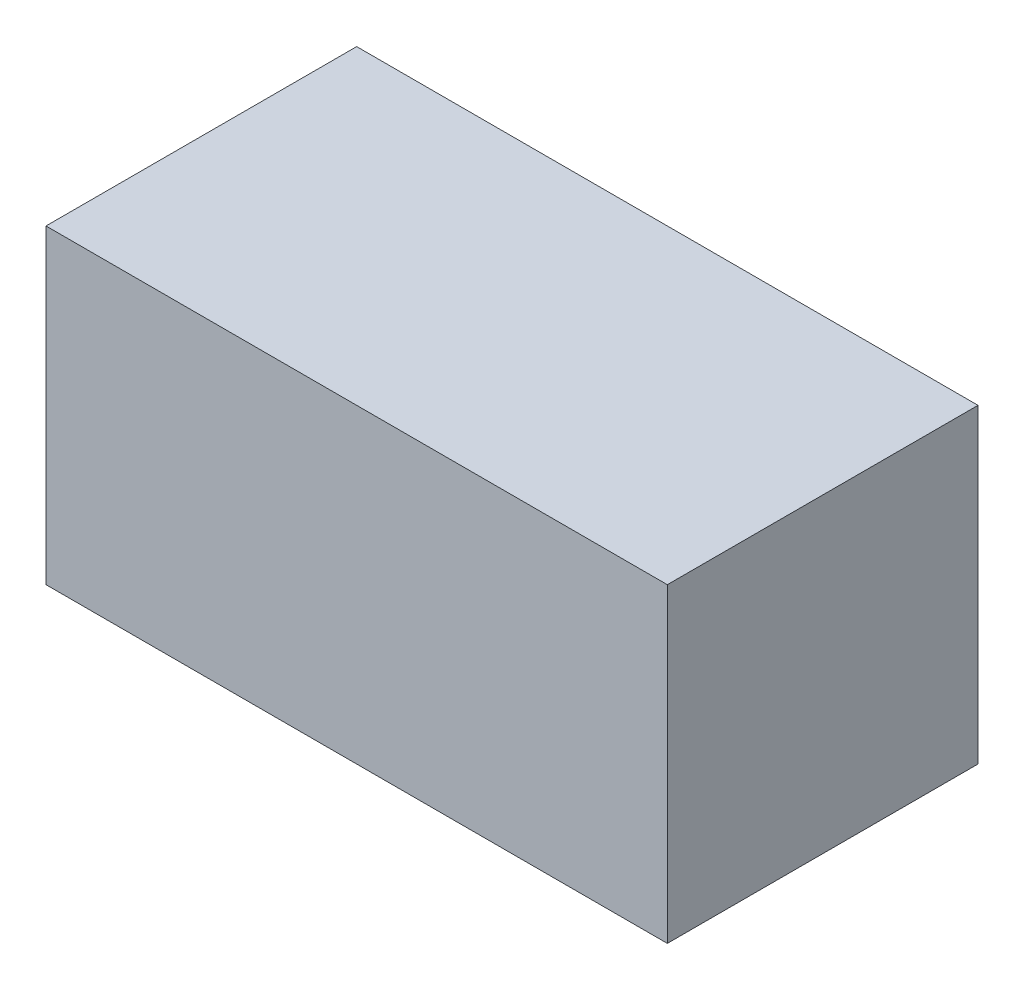
SolidWorks part; units mm, degrees
ref_plane "Front Plane" through (0, 0, 0) normal (0, 0, 1) x (1, 0, 0)
ref_plane "Top Plane" through (0, 0, 0) normal (0, 1, 0) x (1, 0, 0)
ref_plane "Right Plane" through (0, 0, 0) normal (1, 0, 0) x (0, 0, -1)
sketch "Sketch1" plane through (0, 0, 0) normal (0, 1, 0) x (1, 0, 0)
  line L0 (0, 0) -> (-45, 0)
  line L1 (-45, 0) -> (-45, 45)
  line L2 (-45, 45) -> (9.6729, 45)
  line L3 (9.6729, 45) -> (45, 45)
  line L4 (45, 45) -> (45, 0)
  line L5 (45, 0) -> (0, 0)
  point P7 (-55.8505, 45)
  point P8 (0, 0)
  point P9 (0, 0)
  dimension "D2" = 45
  dimension "D3" = 45
extrude "Boss-Extrude1" add sketch "Sketch1" along normal blind 45
